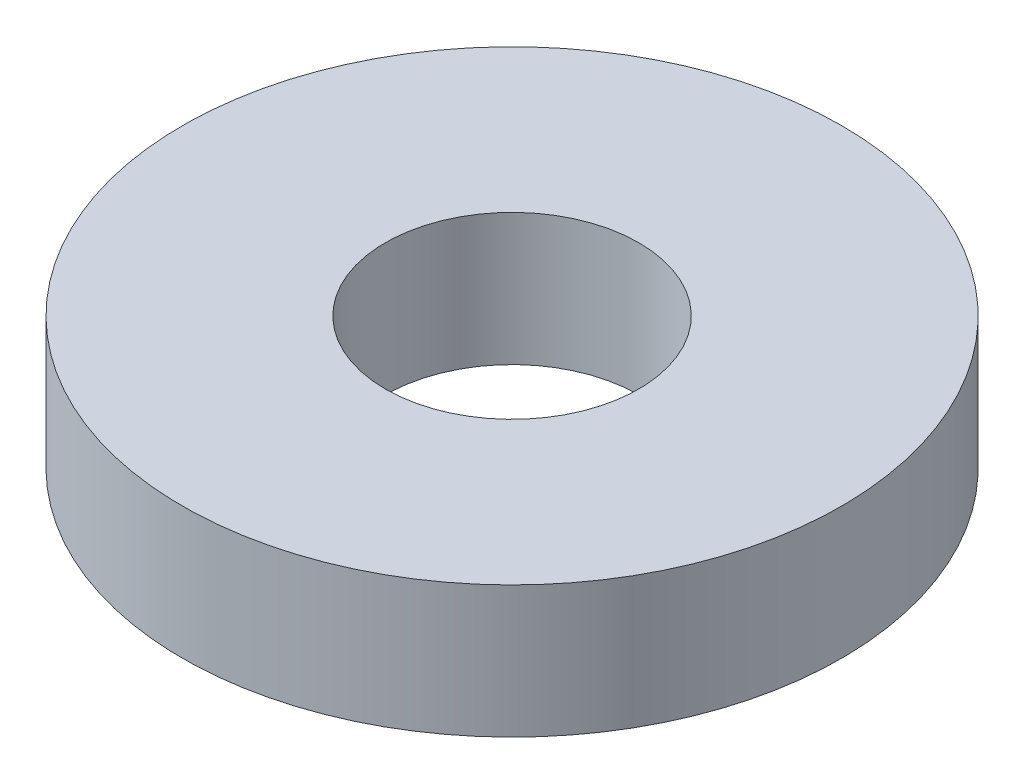
SolidWorks part; units mm, degrees
ref_plane "Front Plane" through (0, 0, 0) normal (0, 0, 1) x (1, 0, 0)
ref_plane "Top Plane" through (0, 0, 0) normal (0, 1, 0) x (1, 0, 0)
ref_plane "Right Plane" through (0, 0, 0) normal (1, 0, 0) x (0, 0, -1)
sketch "Sketch1" plane through (0, 0, 0) normal (0, 1, 0) x (1, 0, 0)
  circle A0 centre (0, 0) radius 65
  dimension "FLANGE_OD" = 130
extrude "Boss-Extrude1" add sketch "Sketch1" along normal blind 26
sketch "Sketch2" plane through (0, 0, 0) normal (0, 1, 0) x (1, 0, 0)
  circle A0 centre (0, 0) radius 25
  dimension "BORE_D" = 50
extrude "Cut-Extrude1" cut sketch "Sketch2" along normal through all
sketch "Sketch3" plane through (0, 26, 0) normal (0, 1, 0) x (1, 0, 0)
  circle A0 centre (0, 0) radius 15.7173 construction
  circle A1 centre (-15.7173, 0) radius 2.3579
  dimension "BOLT_D" = 4.7157
  dimension "BOLT_PCD" = 31.4347
extrude "Cut-Extrude2" cut sketch "Sketch3" against normal blind 19.1004 rebuild error yes
pattern_circular "CirPattern1" count 4 over 360 rebuild error yes
